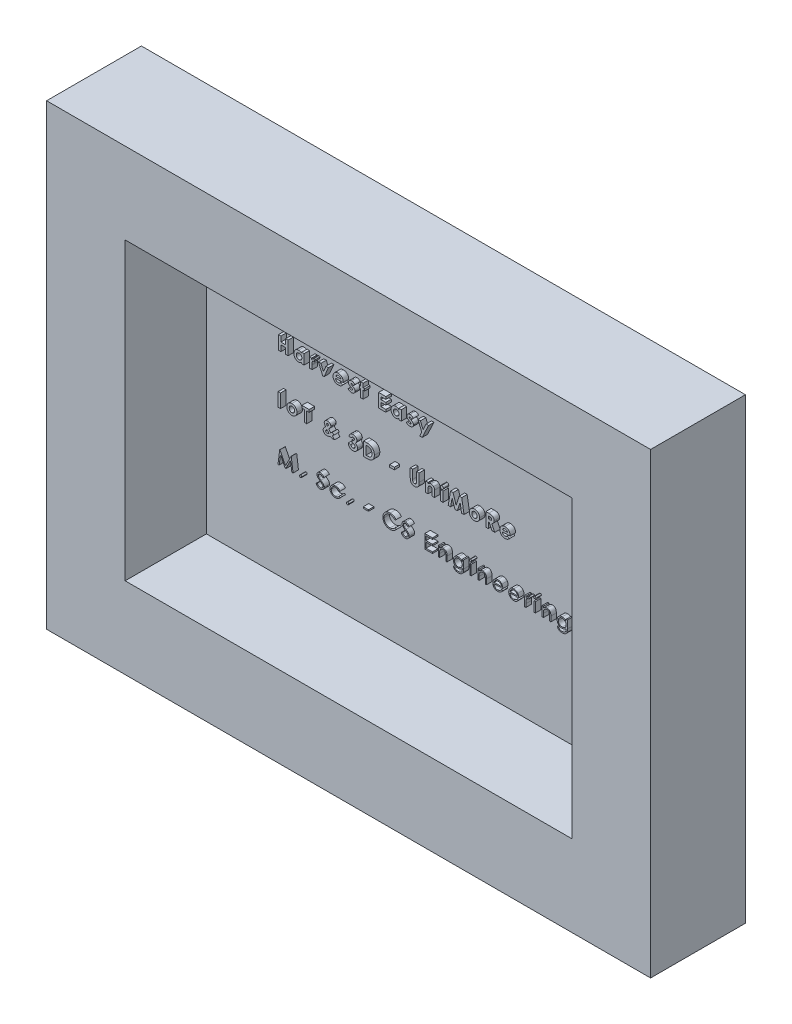
SolidWorks part; units mm, degrees
ref_plane "Piano frontale" through (0, 0, 0) normal (0, 0, 1) x (1, 0, 0)
ref_plane "Piano superiore" through (0, 0, 0) normal (0, 1, 0) x (1, 0, 0)
ref_plane "Piano destro" through (0, 0, 0) normal (1, 0, 0) x (0, 0, -1)
sketch "Schizzo1" plane through (0, 0, 0) normal (0, 0, 1) x (1, 0, 0)
  line L0 (-111.6628, 57.7847) -> (111.3372, 57.7847)
  line L1 (111.3372, 57.7847) -> (111.3372, -111.2153)
  line L2 (111.3372, -111.2153) -> (-111.6628, -111.2153)
  line L3 (-111.6628, -111.2153) -> (-111.6628, 57.7847)
  line L4 (-82.6628, 27.7847) -> (-82.6628, -81.2153)
  line L5 (-82.6628, -81.2153) -> (82.3372, -81.2153)
  line L6 (82.3372, -81.2153) -> (82.3372, 27.7847)
  line L7 (82.3372, 27.7847) -> (-82.6628, 27.7847)
  line L8 (-0.1628, 57.7847) -> (-0.1628, 27.7847) construction
  line L9 (-0.1628, -81.2153) -> (-0.1628, -111.2153) construction
  dimension "D1" = 223
  dimension "D2" = 169
  dimension "D3" = 30
  dimension "D4" = 30
  dimension "D5" = 169
  dimension "D6" = 223
  dimension "D7" = 29
  dimension "D8" = 29
extrude "Estrusione-Estrusione2" add sketch "Schizzo1" along normal blind 5 contours L7 L4 L5 L6
extrude "Estrusione-Estrusione3" add sketch "Schizzo1<5>" along normal blind 35
sketch "Schizzo1<5>" plane through (0, 0, 0) normal (0, 0, 1) x (1, 0, 0) same geometry as "Schizzo1"
sketch "Schizzo3" plane through (0, 0, 5) normal (0, 0, 1) x (1, 0, 0)
  text T0 "<b>Harvest Easy</b>\r\n\r\n<b>IoT & 3D - UniMoRe</b>\r\n\r\nM. Sc. - CS Engineering" font "Century Gothic" height 5
extrude "Estrusione-Estrusione4" add sketch "Schizzo3" along normal blind 2
